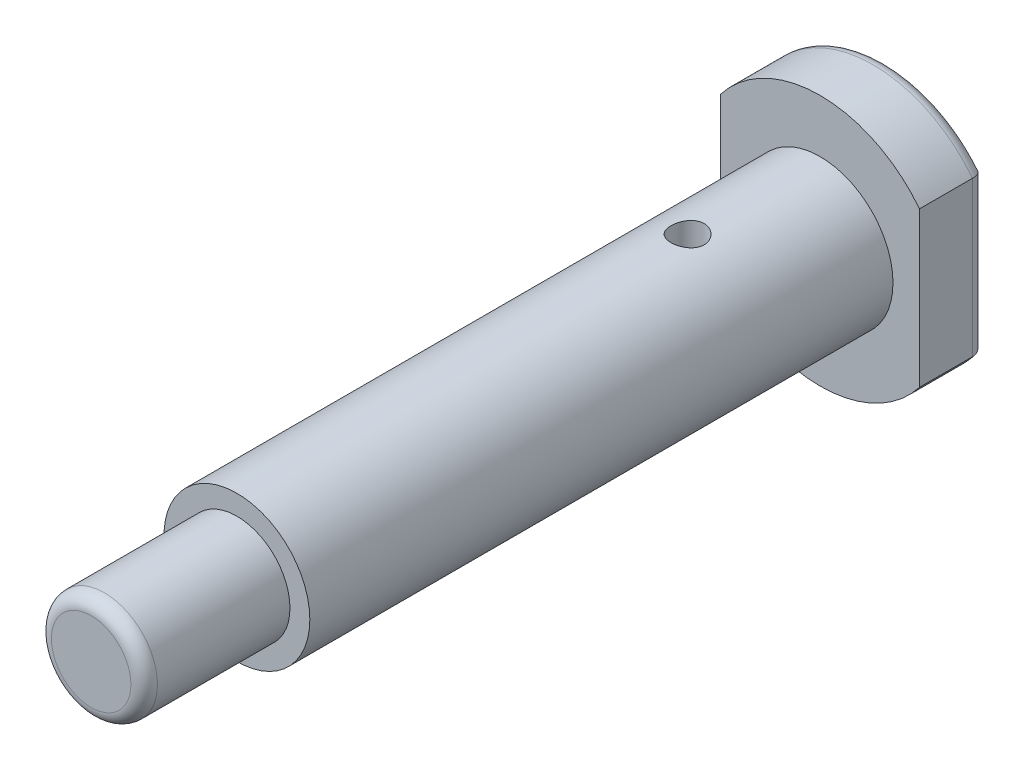
SolidWorks part; units mm, degrees
ref_plane "Front" through (0, 0, 0) normal (0, 0, 1) x (1, 0, 0)
ref_plane "Top" through (0, 0, 0) normal (0, 1, 0) x (1, 0, 0)
ref_plane "Right" through (0, 0, 0) normal (1, 0, 0) x (0, 0, -1)
sketch "Sketch1" plane through (0, 0, 0) normal (0, 0, 1) x (1, 0, 0)
  line L0 (-32.8522, 0) -> (-47.8522, 0)
  line L1 (-47.8522, 0) -> (-17.8522, 0)
  line L2 (-17.8522, 0) -> (-17.8522, 11.6619)
  line L3 (-17.8522, 11.6619) -> (-17.8522, -11.6619)
  line L4 (-47.8522, 0) -> (-47.8522, 11.6619)
  line L5 (-47.8522, 11.6619) -> (-47.8522, -11.6619)
  arc A0 (-47.8522, -11.6619) -> (-17.8522, -11.6619) centre (-32.8522, 0) ccw
  circle A1 centre (-32.8522, 0) radius 11
  circle A2 centre (-32.8522, 0) radius 8
  arc A3 (-47.8522, -9.9499) -> (-17.8522, -9.9499) centre (-32.8522, 0) ccw
  arc A4 (-17.8522, 11.6619) -> (-47.8522, 11.6619) centre (-32.8522, 0) ccw
  arc A5 (-17.8522, 9.9499) -> (-47.8522, 9.9499) centre (-32.8522, 0) ccw
extrude "Boss-Extrude1" add sketch "Sketch1" along normal blind 120 contours L1 A2 L0 | L0 A2 L1 region at (-32.8522, -3.3953, 0) region at (-32.8522, 3.3953, 0)
cosmetic thread "Cosmetic Thread1" parameters "D1"=5, "D2"=15
extrude "Boss-Extrude2" add sketch "Sketch1<3>" along normal blind 98 contours A2 L1 A1 | A2 L1 A1 region at (-32.8522, -8.246, 0) region at (-42.3522, 0.246, 0)
sketch "Sketch1<3>" plane through (0, 0, 0) normal (0, 0, 1) x (1, 0, 0) same geometry as "Sketch1"
extrude "Boss-Extrude3" add sketch "Sketch1<4>" along normal blind 10 contours L2 A5 L4 L1 A1 | L5 A3 L3 L1 A1 region at (-32.8522, -11.3499, 0) region at (-45.8522, 0.3499, 0)
sketch "Sketch1<4>" plane through (0, 0, 0) normal (0, 0, 1) x (1, 0, 0) same geometry as "Sketch1"
extrude "Boss-Extrude4" add sketch "Sketch1<6>" along normal blind 10 contours A5 L3 A4 L5 | A3 L5 A0 L3 region at (-47.5389, 10.8059, 0) region at (-32.8522, -18.3134, 0)
sketch "Sketch1<6>" plane through (0, 0, 0) normal (0, 0, 1) x (1, 0, 0) same geometry as "Sketch1"
fillet "Fillet5" radius 2 4 edges at (-32.8522, -19, 0) (-17.8522, 0, 0) (-32.8522, 19, 0) (-47.8522, 0, 0)
fillet "Fillet6" radius 2 1 edges at (-24.8522, 0, 120)
ref_plane "Plane2" through (0, 11, 0) normal (0, 1, 0) x (1, 0, 0)
sketch "Sketch2" plane through (0, 11, 0) normal (0, 1, 0) x (1, 0, 0)
  line L0 (-32.8522, -10) -> (-32.8522, -30)
  line L1 (-47.8522, -10) -> (-17.8522, -10) construction
  circle A0 centre (-32.8522, -30) radius 2.5
extrude "Cut-Extrude1" cut sketch "Sketch2" against normal blind 100 contours A0 region at (-34.57, 11, 31.7178)
